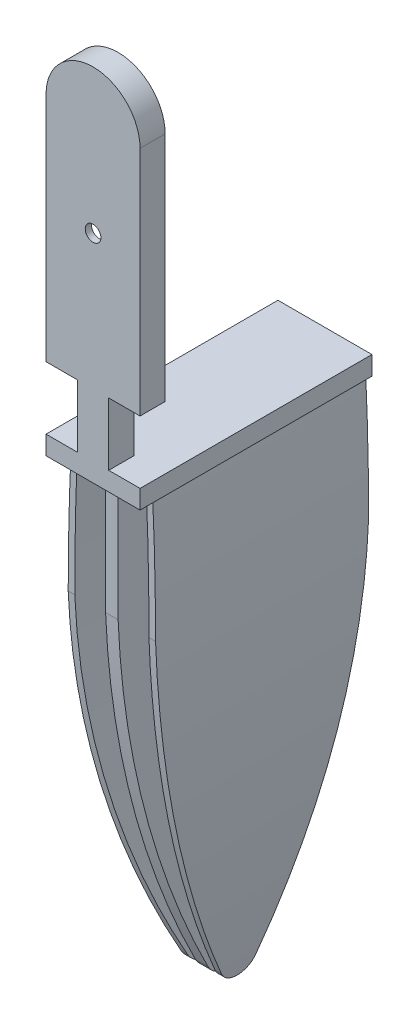
SolidWorks part; units mm, degrees
ref_plane "前基準面" through (0, 0, 0) normal (0, 0, 1) x (1, 0, 0)
ref_plane "上基準面" through (0, 0, 0) normal (0, 1, 0) x (1, 0, 0)
ref_plane "右基準面" through (0, 0, 0) normal (1, 0, 0) x (0, 0, -1)
sketch "草圖1" plane through (0, 0, 0) normal (0, 0, 1) x (1, 0, 0)
  line L0 (0, 0) -> (0, 4.6483) construction
  line L1 (7.5, 8) -> (7.5, 55)
  line L3 (-7.5, 8) -> (-7.5, 55)
  line L4 (-7.5, 8) -> (7.5, 8)
  line L5 (7.5, 4.6483) -> (-12.1697, 4.6483) construction
  arc A1 (7.5, 55) -> (-7.5, 55) centre (0, 55) ccw
  dimension "D1" = 47
extrude "填料-伸長1" add sketch "草圖1" along normal blind 2 and the other way blind 2
sketch "草圖3" plane through (0, 0, 0) normal (0, 0, 1) x (1, 0, 0)
  line L12 (0, -2.2) -> (0, 2.2) construction
  line L19 (-2.1062, 57.3548) -> (-4.9325, 40.3238)
  line L20 (2.1062, 57.3548) -> (4.9325, 40.3238)
  line L21 (2.1062, 21.6557) -> (4.9325, 38.6867)
  line L22 (-2.1062, 21.6557) -> (-4.9325, 38.6867)
  arc A9 (-4.9325, 40.3238) -> (-4.9325, 38.6867) centre (0, 39.5053) ccw
  arc A10 (2.1062, 57.3548) -> (-2.1062, 57.3548) centre (0, 57.0053) ccw
  arc A11 (2.1062, 21.6557) -> (-2.1062, 21.6557) centre (0, 22.0053) cw
  arc A12 (4.9325, 38.6867) -> (4.9325, 40.3238) centre (0, 39.5053) ccw
  dimension "D4" = 17.5
  dimension "D2" = 10
  dimension "D3" = 4.27
sketch "草圖6" plane through (0, 0, 0) normal (1, 0, 0) x (0, 0, -1)
  line L0 (-2, 8) -> (-2, 5)
  line L7 (-2, 8) -> (35, 8)
  line L9 (-2, 5) -> (35, 5)
  line L10 (35, 8) -> (35, 5)
extrude "填料-伸長2" add sketch "草圖6" along normal blind 7.5 and the other way blind 7.5
sketch "草圖8" plane through (0, 0, 0) normal (1, 0, 0) x (0, 0, -1)
  line L0 (18, 5) -> (18, -75) construction
  line L1 (-2, 5) -> (35, 5) construction
  line L2 (35, 5) -> (35, 8) construction
  line L3 (1, 5) -> (1, -0.7692) construction
  line L12 (1, 5) -> (35, 5)
  line L26 (35, 5) -> (35, -14.9047)
  line L27 (1, 5) -> (1, -14.9047)
  arc A7 (35, -14.9047) -> (18, -75) centre (-98.6891, -9.5384) cw
  arc A8 (1, -14.9047) -> (18, -75) centre (134.6891, -9.5384) ccw
  dimension "D1" = 17
  dimension "D2" = 17
  dimension "D3" = 80
extrude "填料-伸長4" add sketch "草圖8" along normal blind 1 and the other way blind 1 contours L26 A7 A8 L27 L12
sketch "草圖9" plane through (0, 0, 0) normal (1, 0, 0) x (0, 0, -1)
  line L0 (13.1021, 5.3065) -> (3.1021, 5.3065)
  line L1 (35.3755, -19.5858) -> (35.3755, -51.6928)
  line L2 (-1.8979, -16.6928) -> (-1.8979, -51.6928)
  arc A0 (35.3755, -51.6928) -> (25.3756, -64.9105) centre (17.6733, -48.6917) cw
  arc A1 (-1.8979, -51.6928) -> (8.102, -64.9105) centre (15.8043, -48.6917) ccw
  arc A2 (25.3756, -64.9105) -> (8.102, -64.9105) centre (16.7388, -64.9105) ccw
  arc A3 (13.1021, 5.3065) -> (35.3755, -19.5858) centre (-8.8884, -36.7816) cw
  arc A4 (3.1021, 5.3065) -> (-1.8979, -16.6928) centre (36.6834, -13.8937) ccw
fillet "圓角1" radius 3 1 edges at (0, -75, -18) type face fillet first side face at (0, -45.4553, -7.7223) second side face at (0, -45.4553, -28.2777)
ref_plane "平面5" through (0, 5, 0) normal (0, -1, 0) x (-1, 0, 0)
sketch "草圖14" plane through (0, 5, 0) normal (0, -1, 0) x (-1, 0, 0)
  line L0 (0, 1.0386) -> (9.1016, 1.0386) construction
  line L1 (0, 3.1021) -> (0, -1.9993) construction
  line L2 (0, 36.708) -> (0, -1.0851) construction
  line L3 (0, 22.5803) -> (0, -22.5803) construction
  line L4 (-1, 35) -> (-7.5, 35) construction
  line L5 (-5.5, 1) -> (-6.5, 1)
  line L6 (-5.5, 1) -> (-5.5, 35)
  line L7 (-5.5, 35) -> (-6.5, 35)
  line L8 (-6.5, 1) -> (-6.5, 35)
  point P14 (0, 17.8114)
  dimension "D1" = 34
  dimension "D2" = 1
  dimension "D3" = 5.5
ref_plane "平面6" through (0, -71.5, 0) normal (0, -1, 0) x (-1, 0, 0)
sketch "草圖15" plane through (0, -71.5, 0) normal (0, -1, 0) x (-1, 0, 0)
  line L0 (-1, 18) -> (13.7949, 18) construction
  line L1 (-1, 20.6764) -> (-1, 15.3236) construction
  line L2 (0, 36.708) -> (0, -4.347) construction
  line L3 (0, 22.5803) -> (0, -22.5803) construction
  line L5 (-3, 18.5) -> (-2, 18.5)
  line L6 (-3, 18.5) -> (-3, 17.5)
  line L7 (-3, 17.5) -> (-2, 17.5)
  line L8 (-2, 18.5) -> (-2, 17.5)
  dimension "D1" = 1
  dimension "D2" = 1
  dimension "D3" = 2
ref_plane "平面10" through (0, 0, -18) normal (0, 0, 1) x (1, 0, 0)
sketch "草圖19" plane through (0, 0, -18) normal (0, 0, 1) x (1, 0, 0)
  line L0 (5.5, 5) -> (6.5, 5) construction
  line L1 (-8.25, 5) -> (8.25, 5) construction
  line L2 (3, -71.5) -> (2, -71.5) construction
  line L3 (-8.25, -71.5) -> (8.25, -71.5) construction
  line L4 (3, -71.5) -> (2, -71.5) construction
  line L5 (6.5, 5) -> (5.5, 5)
  line L6 (3, -71.5) -> (2, -71.5)
  line L7 (0, 14.5058) -> (0, -84.4476) construction
  line L8 (0, -22.5803) -> (0, 22.5803) construction
  line L9 (-3, -71.5) -> (-2, -71.5)
  line L10 (-6.5, 5) -> (-5.5, 5)
  arc A0 (5.5, 5) -> (2, -71.5) centre (-420, -13.8627) cw
  arc A1 (6.5, 5) -> (3, -71.5) centre (-403.5134, -14.5713) cw
  arc A2 (-6.5, 5) -> (-3, -71.5) centre (403.5134, -14.5713) ccw
  arc A3 (-5.5, 5) -> (-2, -71.5) centre (420, -13.8627) ccw
extrude "填料-伸長8" add sketch "草圖19" along normal blind 17 and the other way blind 17
sketch "草圖20" plane through (0, 0, 0) normal (1, 0, 0) x (0, 0, -1)
  line L0 (18, 65.5251) -> (18, -80.6829) construction
  line L1 (18, 11.7122) -> (18, -11.7122) construction
  line L5 (1, -14.9047) -> (1, -76.9405)
  line L6 (1, -76.9405) -> (35, -76.9405)
  line L7 (35, -76.9405) -> (35, -14.9047)
  arc A0 (35, -14.9047) -> (18, -75) centre (-98.6891, -9.5384) cw
  arc A1 (1, -14.9047) -> (18, -75) centre (134.6891, -9.5384) ccw
  point P14 (18, 5)
extrude "除料-伸長3" cut sketch "草圖20" against normal blind 17.5 and the other way blind 17.5
fillet "圓角7" radius 3 1 edges at (2.5, -71.5, -16.1044) type face fillet first side face at (2.5, -71.5, -18) second side face at (4.8165, -43.5187, -7.3429)
fillet "圓角8" radius 3 1 edges at (2.5, -71.5, -19.8956) type face fillet first side face at (2.5, -71.5, -18.9157) second side face at (4.8191, -43.5732, -28.6427)
fillet "圓角9" radius 3 1 edges at (-2.5, -71.5, -16.1044) type face fillet first side face at (-4.8191, -43.5732, -7.3573) second side face at (-2.5, -71.5, -18)
fillet "圓角10" radius 3 1 edges at (-2.5, -71.5, -19.8956) type face fillet first side face at (-4.8165, -43.5187, -28.6571) second side face at (-2.5, -71.5, -18.9157)
ref_plane "平面11" through (0, 0, 2) normal (0, 0, 1) x (1, 0, 0)
sketch "草圖21" plane through (0, 0, 2) normal (0, 0, 1) x (1, 0, 0)
  line L0 (-7.5, 55) -> (-7.5, 5) construction
  line L1 (-7.5, 8) -> (-2.5, 8)
  line L2 (-7.5, 8) -> (-7.5, 18)
  line L3 (-7.5, 18) -> (-2.5, 18)
  line L4 (-2.5, 8) -> (-2.5, 18)
  line L5 (0, 20.9814) -> (0, -1.1685) construction
  line L6 (7.5, 18) -> (2.5, 18)
  line L7 (2.5, 8) -> (2.5, 18)
  line L8 (7.5, 8) -> (2.5, 8)
  line L9 (7.5, 8) -> (7.5, 18)
  line L10 (-8.25, 5) -> (8.25, 5) construction
  dimension "D1" = 10
  dimension "D2" = 5
  dimension "D3" = 3
extrude "除料-伸長4" cut sketch "草圖21" against normal blind 4
ref_plane "平面12" through (0, 0, -2) normal (0, 0, -1) x (-1, 0, 0)
sketch "草圖22" plane through (0, 0, -2) normal (0, 0, -1) x (-1, 0, 0)
  line L0 (0, 69.272) -> (0, -23.2008) construction
  line L1 (0, 22.5803) -> (0, -22.5803) construction
  line L2 (0, -14.9047) -> (0, -75) construction
  line L3 (2.5, 8) -> (-2.5, 8)
  line L4 (7.5, 8) -> (-7.5, 8) construction
  line L5 (-2.5, 18) -> (-2.5, 8) construction
  line L6 (-2.5, 8) -> (-2.5, 18)
  line L7 (-2.5, 18) -> (-7.5, 18)
  line L8 (-7.5, 18) -> (-7.5, 55)
  line L9 (2.5, 8) -> (2.5, 18)
  line L10 (2.5, 18) -> (7.5, 18)
  line L11 (7.5, 18) -> (7.5, 55)
  arc A0 (-7.5, 55) -> (0, 62.4923) centre (-0.0077, 55) cw
  arc A1 (7.5, 55) -> (0, 62.4923) centre (0.0077, 55) ccw
  point P21 (0, 8)
extrude "除料-伸長5" cut sketch "草圖3" against normal blind 2 and the other way blind 1
sketch "草圖23" plane through (0, 0, -2) normal (0, 0, -1) x (-1, 0, 0)
  line L0 (-5, 39.5053) -> (5, 39.5053) construction
  arc A0 (-4.9325, 40.3238) -> (-4.9325, 38.6867) centre (0, 39.5053) ccw construction
  arc A1 (4.9325, 38.6867) -> (4.9325, 40.3238) centre (0, 39.5053) ccw construction
  circle A2 centre (0, 39.5053) radius 1.25
  dimension "D1" = 2.5
extrude "除料-伸長6" cut sketch "草圖23" against normal blind 13
